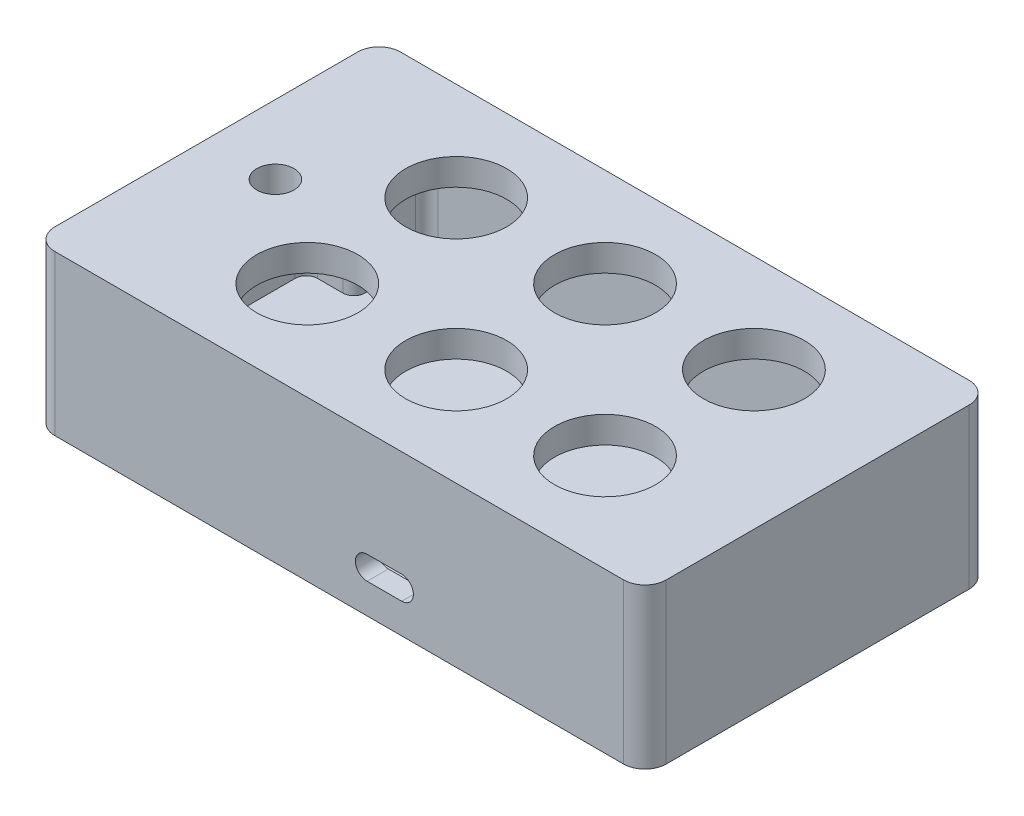
SolidWorks part; units mm, degrees
ref_plane "Front Plane" through (0, 0, 0) normal (0, 0, 1) x (1, 0, 0)
ref_plane "Top Plane" through (0, 0, 0) normal (0, 1, 0) x (1, 0, 0)
ref_plane "Right Plane" through (0, 0, 0) normal (1, 0, 0) x (0, 0, -1)
sketch "Sketch1" plane through (0, 0, 0) normal (0, 1, 0) x (1, 0, 0)
  line L0 (6.1, 47.3145) -> (10.8617, 47.3145)
  line L5 (0, 0) -> (115, 0)
  line L6 (0, 0) -> (0, 65)
  line L7 (0, 65) -> (115, 65)
  line L8 (115, 0) -> (115, 65)
  line L9 (12.9617, 49.4145) -> (12.9617, 58.9)
  line L10 (15.0617, 61) -> (100.6229, 61)
  line L11 (102.7229, 58.9) -> (102.7229, 44.6015)
  line L12 (104.8229, 42.5015) -> (108.9, 42.5015)
  line L13 (111, 40.4015) -> (111, 14.6015)
  line L14 (108.9, 12.5015) -> (105.2066, 12.5015)
  line L15 (103.1066, 10.4015) -> (103.1066, 6.1)
  line L16 (101.0066, 4) -> (18.2066, 4)
  line L17 (16.1066, 6.1) -> (16.1066, 19.1831)
  line L18 (14.0066, 21.2831) -> (6.1, 21.2831)
  line L19 (4, 23.3831) -> (4, 45.2145)
  line L20 (4, 47.3145) -> (0, 47.3145) construction
  line L21 (111, 42.5015) -> (115, 42.5015) construction
  line L22 (12.9617, 61) -> (12.9617, 65) construction
  line L23 (16.1066, 4) -> (16.1066, 0) construction
  line L24 (57.5, 65) -> (57.5, 0) construction
  line L26 (115, 32.5) -> (0, 32.5) construction
  circle A5 centre (108.9, 50.0015) radius 2.1
  circle A6 centre (110.6851, 6.4043) radius 2.1
  circle A7 centre (7.7851, 14.6015) radius 2.1
  circle A8 centre (7.7851, 55.6015) radius 2.1
  arc A9 (6.1, 21.2831) -> (4, 23.3831) centre (6.1, 23.3831) cw
  arc A10 (16.1066, 19.1831) -> (14.0066, 21.2831) centre (14.0066, 19.1831) ccw
  arc A11 (18.2066, 4) -> (16.1066, 6.1) centre (18.2066, 6.1) cw
  arc A12 (103.1066, 6.1) -> (101.0066, 4) centre (101.0066, 6.1) cw
  arc A13 (105.2066, 12.5015) -> (103.1066, 10.4015) centre (105.2066, 10.4015) ccw
  arc A14 (111, 14.6015) -> (108.9, 12.5015) centre (108.9, 14.6015) cw
  arc A15 (108.9, 42.5015) -> (111, 40.4015) centre (108.9, 40.4015) cw
  arc A16 (102.7229, 44.6015) -> (104.8229, 42.5015) centre (104.8229, 44.6015) ccw
  arc A17 (100.6229, 61) -> (102.7229, 58.9) centre (100.6229, 58.9) cw
  arc A18 (12.9617, 58.9) -> (15.0617, 61) centre (15.0617, 58.9) cw
  arc A19 (10.8617, 47.3145) -> (12.9617, 49.4145) centre (10.8617, 49.4145) ccw
  arc A20 (6.1, 47.3145) -> (4, 45.2145) centre (6.1, 45.2145) ccw
  point P43 (111, 12.5015)
  dimension "D3" = 30
  dimension "D6" = 4.2
  dimension "D7" = 2.1
  dimension "D1" = 115
  dimension "D2" = 65
  dimension "D4" = 107
  dimension "D5" = 57
  dimension "D8" = 35.4
  dimension "D9" = 41
  dimension "D10" = 87
  dimension "D11" = 102.9
extrude "Boss-Extrude1" add sketch "Sketch1" along normal blind 22
sketch "Sketch6" plane through (0, 0, 0) normal (0, -1, 0) x (1, 0, 0)
  line L4 (0, 0) -> (0, -65)
  line L5 (0, -65) -> (115, -65)
  line L6 (115, -65) -> (115, 0)
  line L7 (115, 0) -> (0, 0)
  line L8 (0, 0) -> (0, -65)
  line L9 (0, -65) -> (115, -65)
  line L10 (115, -65) -> (115, 0)
  line L11 (115, 0) -> (0, 0)
  circle A4 centre (7.7851, -14.6015) radius 2.1
  circle A5 centre (110.6851, -6.4043) radius 2.1
  circle A6 centre (108.9, -50.0015) radius 2.1
  circle A7 centre (7.7851, -55.6015) radius 2.1
  circle M5 centre (7.7851, -14.6015) radius 2.1
  circle M6 centre (108.9, -50.0015) radius 2.1
  line M7 (0, 0) -> (0, -65)
  line M8 (0, -65) -> (115, -65)
  line M9 (115, -65) -> (115, 0)
  line M10 (115, 0) -> (0, 0)
  circle M11 centre (110.6851, -6.4043) radius 2.1
  circle M12 centre (7.7851, -55.6015) radius 2.1
  line M13 (4, -45.2145) -> (4, -23.3831)
  arc M14 (4, -23.3831) -> (6.1, -21.2831) centre (6.1, -23.3831) cw
  line M15 (6.1, -21.2831) -> (14.0066, -21.2831)
  arc M16 (14.0066, -21.2831) -> (16.1066, -19.1831) centre (14.0066, -19.1831) ccw
  line M17 (16.1066, -19.1831) -> (16.1066, -6.1)
  arc M18 (16.1066, -6.1) -> (18.2066, -4) centre (18.2066, -6.1) cw
  line M19 (18.2066, -4) -> (101.0066, -4)
  arc M20 (101.0066, -4) -> (103.1066, -6.1) centre (101.0066, -6.1) cw
  line M21 (103.1066, -6.1) -> (103.1066, -10.4015)
  arc M22 (103.1066, -10.4015) -> (105.2066, -12.5015) centre (105.2066, -10.4015) ccw
  line M23 (105.2066, -12.5015) -> (108.9, -12.5015)
  arc M24 (108.9, -12.5015) -> (111, -14.6015) centre (108.9, -14.6015) cw
  line M25 (111, -14.6015) -> (111, -40.4015)
  arc M26 (111, -40.4015) -> (108.9, -42.5015) centre (108.9, -40.4015) cw
  line M27 (108.9, -42.5015) -> (104.8229, -42.5015)
  arc M28 (104.8229, -42.5015) -> (102.7229, -44.6015) centre (104.8229, -44.6015) ccw
  line M29 (102.7229, -44.6015) -> (102.7229, -58.9)
  arc M30 (102.7229, -58.9) -> (100.6229, -61) centre (100.6229, -58.9) cw
  line M31 (100.6229, -61) -> (15.0617, -61)
  arc M32 (15.0617, -61) -> (12.9617, -58.9) centre (15.0617, -58.9) cw
  line M33 (12.9617, -58.9) -> (12.9617, -49.4145)
  arc M34 (12.9617, -49.4145) -> (10.8617, -47.3145) centre (10.8617, -49.4145) ccw
  line M35 (10.8617, -47.3145) -> (6.1, -47.3145)
  arc M36 (6.1, -47.3145) -> (4, -45.2145) centre (6.1, -45.2145) cw
  dimension "D1" = 0
extrude "Boss-Extrude4" add sketch "Sketch6" along normal blind 3 contours M10 M7 M8 M9 M6 M11 M36 M13 M14 M15 M16 M17 M18 M19 M20 M21 M22 M23 M24 M25 M26 M27 M28 M29 M30 M31 M32 M33 M34 M35 M12 M5 | M13 M36 M35 M34 M33 M32 M31 M30 M29 M28 M27 M26 M25 M24 M23 M22 M21 M20 M19 M18 M17 M16 M15 M14 region at (57.5, 0, -1.321) region at (58.4122, 0, -32.5322)
sketch "Sketch7" plane through (0, 22, 0) normal (0, 1, 0) x (1, 0, 0)
  line L1 (0, 65) -> (115, 65)
  line L2 (0, 65) -> (0, 0)
  line L3 (0, 0) -> (115, 0)
  line L4 (115, 65) -> (115, 0)
extrude "Boss-Extrude5" add sketch "Sketch7" along normal blind 5
fillet "Fillet1" radius 4 4 edges at (0, 12, -65) (115, 12, -65) (115, 12, 0) (0, 12, 0)
sketch "Sketch4" plane through (0, 27, 0) normal (0, 1, 0) x (1, 0, 0)
  line L0 (115, 4) -> (115, 61) construction
  line L1 (0, 61) -> (0, 4) construction
  line L5 (33, 46.5) -> (61, 46.5) construction
  line L8 (61, 46.5) -> (89, 46.5) construction
  line L13 (0, 32.5) -> (115, 32.5) construction
  circle A10 centre (33, 46.5) radius 9.5
  circle A11 centre (33, 18.5) radius 9.5
  circle A12 centre (61, 46.5) radius 9.5
  circle A13 centre (89, 46.5) radius 9.5
  circle A14 centre (61, 18.5) radius 9.5
  circle A15 centre (89, 18.5) radius 9.5
  circle A17 centre (13, 32.5) radius 3.5
  point P12 (103.4874, 32.5)
  point P15 (12.5718, 32.5)
  point P16 (110.1425, 32.5)
  point P19 (0, 0)
  point P23 (0, 0)
  point P26 (0, 0)
  point P27 (0, 0)
  point P28 (0, 0)
  point P29 (0, 0)
  point P30 (13.431, 32.5)
  dimension "D1" = 19
  dimension "D2" = 33
  dimension "D5" = 13
  dimension "D6" = 7
  dimension "D3" = 28
  dimension "D4" = 28
extrude "Cut-Extrude1" cut sketch "Sketch4" against normal up to next
sketch "Sketch5" plane through (0, 0, 0) normal (0, 0, 1) x (1, 0, 0)
  line L0 (62.75, 4.855) -> (69.25, 4.855) construction
  line L1 (62.75, 7.055) -> (69.25, 7.055)
  line L2 (62.75, 2.655) -> (69.25, 2.655)
  arc A0 (62.75, 7.055) -> (62.75, 2.655) centre (62.75, 4.855) ccw
  arc A1 (69.25, 2.655) -> (69.25, 7.055) centre (69.25, 4.855) ccw
  point P2 (66, 4.855)
  point P7 (66.004, 4.855)
  point P8 (69.25, 2.6388)
  point P10 (66.004, 4.855)
  dimension "D1" = 2.2
  dimension "D2" = 66
  dimension "D3" = 6.5
  dimension "D4" = 4.855
extrude "Cut-Extrude2" cut sketch "Sketch5" against normal up to next
